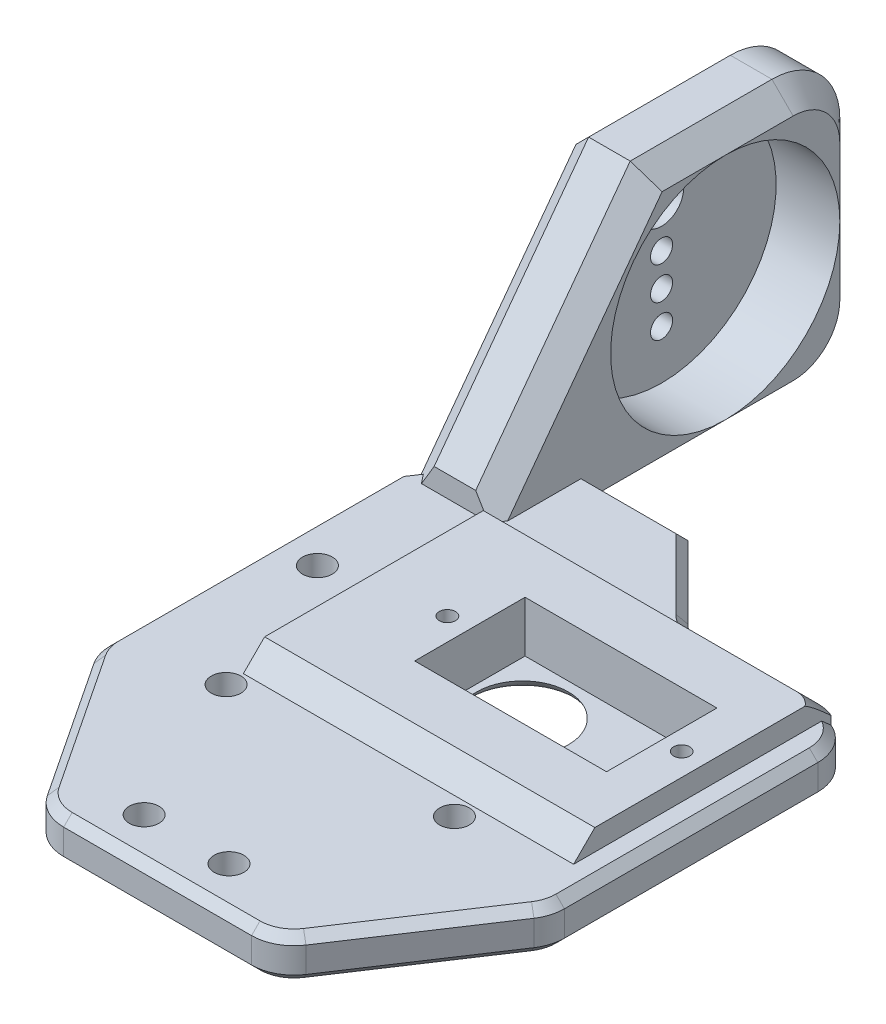
SolidWorks part; units mm, degrees
material "PETG"
ref_plane "Front Plane" through (0, 0, 0) normal (0, 0, 1) x (1, 0, 0)
ref_plane "Top Plane" through (0, 0, 0) normal (0, 1, 0) x (1, 0, 0)
ref_plane "Right Plane" through (0, 0, 0) normal (1, 0, 0) x (0, 0, -1)
sketch "Sketch1" plane through (0, 0, 0) normal (0, 1, 0) x (1, 0, 0)
  line L0 (0, 0) -> (45, 0) construction
  line L1 (45, 15.3791) -> (45, -15.3791)
  line L2 (45, 15.3791) -> (21, 15.3791)
  line L3 (21, 15.3791) -> (11.0015, 25.3776)
  line L4 (11.0015, 25.3776) -> (-4.9985, 25.3776)
  line L5 (-4.9985, 25.3776) -> (-12.2574, 14.4891)
  line L6 (-12.2574, 14.4891) -> (-12.2574, -20.9073)
  line L7 (-12.2574, -20.9073) -> (0.7918, -40.6224)
  line L10 (28.2918, -40.6224) -> (45, -15.3791)
  line L11 (28.2918, -40.6224) -> (0.7918, -40.6224)
  point P6 (45, 0)
  dimension "D2" = 24
  dimension "D3" = 14.14
  dimension "D4" = 225
  dimension "D5" = 16
  dimension "D6" = 27.5
  dimension "D7" = 30.272
  dimension "D8" = 146.31
  dimension "D9" = 123.5
  dimension "D10" = 123.5
  dimension "D11" = 23.6425
  dimension "D13" = 45
  dimension "D1267.5" = 66
extrude "Boss-Extrude1" add sketch "Sketch1" along normal blind 5
sketch "Sketch2" plane through (0, 5, 0) normal (0, 1, 0) x (1, 0, 0)
  line L0 (45, 0) -> (-23.0301, 0) construction
  line L1 (45, -15.3791) -> (45, 15.3791) construction
  line L3 (-12.2574, 14.4891) -> (-12.2574, -20.9073) construction
  line L9 (11.5, 5.4) -> (22.3, 5.4)
  line L10 (11.5, 5.4) -> (11.5, -5.4)
  line L11 (11.5, -5.4) -> (22.3, -5.4)
  line L12 (22.3, 5.4) -> (22.3, -5.4)
  line L13 (11.5, 5.4) -> (22.3, -5.4) construction
  line L14 (11.5, -5.4) -> (22.3, 5.4) construction
  circle A0 centre (-7.2574, 0) radius 1.75
  point P9 (-12.2574, -3.2091)
  point P23 (16.9, 0)
  dimension "D2" = 3.5
  dimension "D6" = 10.8
  dimension "D1" = 5
  dimension "D7" = 10.8
  dimension "D8" = 22.7
extrude "Cut-Extrude1" cut sketch "Sketch2" against normal through all
fillet "Fillet1" radius 5.4 4 edges at (11.5, 0, 0) (11.5, 2.5, 5.4) (11.5, 2.5, -5.4) (11.5, 5, 0)
fillet "Fillet2" radius 5.4 8 edges at (22.3, 0, 0) (22.3, 2.5, -5.4) (22.3, 2.5, 5.4) (19.6, 0, -5.4) (22.3, 5, 0) (19.6, 5, -5.4) (19.6, 5, 5.4) (19.6, 0, 5.4)
sketch "Sketch3" plane through (0, 5, 0) normal (0, 1, 0) x (1, 0, 0)
  line L0 (11.5, 0) -> (22.3, 0) construction
  line L1 (45, 15.3791) -> (21, 15.3791) construction
  line L2 (5.4, -6.5) -> (28.4, -6.5)
  line L3 (5.4, -6.5) -> (5.4, 6.5)
  line L4 (5.4, 6.5) -> (28.4, 6.5)
  line L5 (28.4, -6.5) -> (28.4, 6.5)
  line L6 (5.4, -6.5) -> (28.4, 6.5) construction
  line L7 (5.4, 6.5) -> (28.4, -6.5) construction
  line L8 (-0.6, -15.3791) -> (34.4, -15.3791)
  line L9 (-0.6, -15.3791) -> (-0.6, 15.3791)
  line L10 (-0.6, 15.3791) -> (34.4, 15.3791)
  line L11 (34.4, -15.3791) -> (34.4, 15.3791)
  line L12 (-0.6, -15.3791) -> (34.4, 15.3791) construction
  line L13 (-0.6, 15.3791) -> (34.4, -15.3791) construction
  arc A0 (16.9, 5.4) -> (16.9, -5.4) centre (16.9, 0) ccw construction
  arc A1 (16.9, -5.4) -> (16.9, 5.4) centre (16.9, 0) ccw construction
  point P8 (16.9, 0)
  point P13 (16.9, 0)
  dimension "D1" = 6
  dimension "D2" = 13
  dimension "D3" = 23
extrude "Boss-Extrude2" add sketch "Sketch3" along normal blind 2.5
sketch "Sketch4" plane through (0, 5, 0) normal (0, 1, 0) x (1, 0, 0)
  line L4 (5.4, 6.5) -> (5.4, -6.5)
  line L6 (5.4, 6.5) -> (5.4, -6.5)
  line L12 (5.4, -6.5) -> (28.4, -6.5)
  line L13 (5.4, -6.5) -> (28.4, -6.5)
  line L14 (28.4, -6.5) -> (28.4, 6.5)
  line L15 (28.4, -6.5) -> (28.4, 6.5)
  line L16 (28.4, 6.5) -> (5.4, 6.5)
  line L17 (28.4, 6.5) -> (5.4, 6.5)
  dimension "D1" = 0
extrude "Cut-Extrude2" cut sketch "Sketch4" against normal blind 3.5
fillet "Fillet4" radius 4 2 edges at (34.4, 6.25, 15.3791) (34.4, 6.25, -15.3791)
sketch "Sketch6" plane through (0, 0, -25.3776) normal (0, 0, -1) x (-1, 0, 0)
  line L0 (4.9985, 5) -> (4.9985, 0) construction
  line L1 (0.6, 0) -> (10.9985, 0)
  line L2 (0.6, 0) -> (0.6, 32)
  line L3 (0.6, 32) -> (10.9985, 32)
  line L4 (10.9985, 0) -> (10.9985, 32)
  line L5 (-11.0015, 0) -> (4.9985, 0) construction
  line L6 (0.6, 7.5) -> (0.6, 5) construction
  dimension "D2" = 6
  dimension "D3" = 32
extrude "Boss-Extrude3" add sketch "Sketch6" along normal blind 32
fillet "Fillet5" radius 8 2 edges at (-5.7992, 0, -57.3776) (-5.7992, 32, -57.3776)
sketch "Sketch8" plane through (-10.9985, 0, 0) normal (-1, 0, 0) x (0, 0, 1)
  line L1 (-25.3776, 32) -> (-25.3776, 0)
  line L4 (-25.3776, 0) -> (-14.4891, 0)
  line L5 (-14.4891, 0) -> (-14.4891, 7.5)
  line L6 (-15.3791, 7.5) -> (15.3791, 7.5) construction
  line L7 (-25.3776, 32) -> (-14.4891, 7.5)
extrude "Boss-Extrude4" add sketch "Sketch8" against normal up to surface (10.3985 mm away) up to face at (-0.6, 14.4286, -41.8509)
sketch "Sketch10" plane through (-10.9985, 0, 0) normal (-1, 0, 0) x (0, 0, 1)
  line L0 (-14.4891, 7.5) -> (-32.6851, 32)
  line L1 (-49.3776, 32) -> (-25.3776, 32) construction
  line L2 (-32.6851, 32) -> (-25.3776, 32)
  line L3 (-25.3776, 32) -> (-14.4891, 7.5)
  line L4 (-49.3776, 32) -> (-25.3776, 32) construction
  line L5 (-14.4891, 7.5) -> (-25.3776, 32) construction
  dimension "D2" = 30.5179
extrude "Cut-Extrude6" cut sketch "Sketch10" against normal through all
sketch "Sketch11" plane through (0, 1.5, 0) normal (0, 1, 0) x (1, 0, 0)
  line L0 (5.4, -6.5) -> (28.4, -6.5) construction
  line L1 (5.4, 6.5) -> (10.7, 6.5)
  line L2 (5.4, 6.5) -> (5.4, -6.5)
  line L3 (5.4, -6.5) -> (10.7, -6.5)
  line L4 (10.7, 6.5) -> (10.7, -6.5)
  line L5 (5.4, 0) -> (10.7, 0) construction
  circle A0 centre (8.05, 0) radius 0.95
  dimension "D2" = 1.9
  dimension "D1" = 5.3
extrude "Boss-Extrude5" add sketch "Sketch11" along normal up to surface (6 mm away) up to face at (18.4938, 7.5, -2.0699)
sketch "Sketch12" plane through (0, 7.5, 0) normal (0, 1, 0) x (1, 0, 0)
  line L0 (30.4, 15.3791) -> (38.3, 15.3791)
  line L1 (38.3, 15.3791) -> (38.3, -15.3791)
  line L2 (30.4, -15.3791) -> (38.3, -15.3791)
  line L3 (34.4, -11.3791) -> (34.4, 11.3791) construction
  line L4 (34.4, -11.3791) -> (34.4, 11.3791)
  arc A0 (30.4, -15.3791) -> (34.4, -11.3791) centre (30.4, -11.3791) ccw construction
  arc A1 (34.4, 11.3791) -> (30.4, 15.3791) centre (30.4, 11.3791) ccw construction
  arc A2 (30.4, -15.3791) -> (34.4, -11.3791) centre (30.4, -11.3791) ccw
  arc A3 (34.4, 11.3791) -> (30.4, 15.3791) centre (30.4, 11.3791) ccw
  dimension "D1" = 7.9
extrude "Boss-Extrude6" add sketch "Sketch12" against normal up to surface (7.5 mm away)
sketch "Sketch13" plane through (0, 7.5, 0) normal (0, 1, 0) x (1, 0, 0)
  line L0 (8.05, 0) -> (35.65, 0) construction
  circle A0 centre (35.65, 0) radius 0.95
  dimension "D2" = 1.9
  dimension "D1" = 27.6
extrude "Cut-Extrude7" cut sketch "Sketch13" against normal up to surface (6 mm away) up to face at (8.05, 1.5, 0.95)
sketch "Sketch14" plane through (0, 7.5, 0) normal (0, 1, 0) x (1, 0, 0)
  line L1 (28.4, 6.5) -> (33.3, 6.5)
  line L2 (28.4, 6.5) -> (28.4, -6.5)
  line L3 (28.4, -6.5) -> (33.3, -6.5)
  line L4 (33.3, 6.5) -> (33.3, -6.5)
  dimension "D1" = 4.9
extrude "Cut-Extrude8" cut sketch "Sketch14" against normal up to surface (6 mm away) up to face at (19.55, 1.5, 0)
fillet "Fillet11" radius 2.5 2 edges at (11.5, 0, 0) (22.3, 0, 0)
sketch "Sketch16" plane through (0, 0, 0) normal (0, -1, 0) x (1, 0, 0)
  line L0 (16.75, 0) -> (26.4024, 17.5166) construction
  line L1 (26.4024, 17.5166) -> (-0.4976, 17.5166) construction
  line L2 (-2.5177, 35.6224) -> (31.6012, 35.6224) construction
  line L3 (-12.2574, 20.9073) -> (0.7918, 40.6224) construction
  line L4 (28.2918, 40.6224) -> (45, 15.3791) construction
  line L6 (12.9524, 17.5166) -> (12.9524, 35.6224) construction
  line L7 (0.7918, 40.6224) -> (28.2918, 40.6224) construction
  circle A0 centre (26.4024, 17.5166) radius 1.75
  circle A1 centre (-0.4976, 17.5166) radius 1.75
  circle A2 centre (7.9524, 35.6224) radius 1.75
  circle A3 centre (17.9524, 35.6224) radius 1.75
  dimension "D1" = 3.5
  dimension "D5" = 3.5
  dimension "D2" = 26.9
  dimension "D3" = 5
  dimension "D4" = 10
  dimension "D6" = 5
extrude "Cut-Extrude10" cut sketch "Sketch16" against normal up to surface (5 mm away) up to face at (-7.2574, 5, 1.75)
sketch "Sketch17" plane through (38.3, 0, 0) normal (1, 0, 0) x (0, 0, -1)
  line L1 (15.3791, 7.5) -> (-40.6224, 7.5)
  line L2 (15.3791, 7.5) -> (15.3791, 0)
  line L3 (15.3791, 0) -> (-40.6224, 0)
  line L4 (-40.6224, 7.5) -> (-40.6224, 0)
  line L6 (15.3791, 5) -> (15.3791, 7.5) construction
  line L7 (15.3791, 7.5) -> (15.3791, 5) construction
  line L8 (-15.3791, 7.5) -> (15.3791, 7.5) construction
  line L9 (-40.6224, 5) -> (-40.6224, 0) construction
extrude "Cut-Extrude11" cut sketch "Sketch17" along normal up to surface (3.7 mm away) from offset 3 up to face at (45, 2.5, 0)
fillet "Fillet13" radius 5 2 edges at (41.3, 2.5, 20.9692) (41.3, 2.5, -15.3791)
sketch "Sketch19" plane through (-0.6, 0, 0) normal (1, 0, 0) x (0, 0, -1)
  line L0 (57.3776, 24) -> (57.3776, 8) construction
  line L1 (49.3776, 0) -> (25.3776, 0) construction
  circle A0 centre (41.3776, 16) radius 13.5
  dimension "D1" = 27
  dimension "D2" = 16
  dimension "D3" = 16
extrude "Cut-Extrude13" cut sketch "Sketch19" against normal blind 7.5 contours A0
sketch "Sketch20" plane through (-8.1, 0, 0) normal (1, 0, 0) x (0, 0, -1)
  line L0 (41.3776, 29.5) -> (41.3776, 2.5) construction
  circle A0 centre (41.3776, 16) radius 13.5 construction
  circle A1 centre (41.3776, 16) radius 13.5 construction
  circle A2 centre (41.3776, 21.1) radius 2.6
  circle A3 centre (41.3776, 16) radius 1.3
  circle A4 centre (41.3776, 12.14) radius 1.3
  circle A5 centre (41.3776, 8.28) radius 1.3
  dimension "D2" = 5.2
  dimension "D4" = 2.6
  dimension "D1" = 8.4
  dimension "D3" = 5.1
  dimension "D5" = 3.86
  dimension "D6" = 3.86
extrude "Cut-Extrude14" cut sketch "Sketch20" against normal up to surface (2.8985 mm away) up to face at (-10.9985, 12.6111, -34.5825)
chamfer "Chamfer1" distance 2.5 angle 45 3 edges at (37.3215, 7.5, -15.2736) (17.85, 7.5, -15.3791) (18.85, 7.5, 15.3791)
fillet "Fillet15" radius 5 4 edges at (-12.2574, 2.5, 20.9073) (21, 2.5, -15.3791) (0.7918, 2.5, 40.6224) (28.2918, 2.5, 40.6224)
chamfer "Chamfer2" distance 1 angle 45 28 edges at (-12.2574, 0, 2.4566) (-12.2574, 5, 2.4566) (-12.0453, 5, 20.8434) (-12.0453, 0, 20.8434) (-6.059, 5, 30.2721) (-6.059, 0, 30.2721) (1.1118, 5, 40.0269) (1.1118, 0, 40.0269) (14.5418, 5, 40.6224) (14.5418, 0, 40.6224) (27.9718, 5, 40.0269) (27.9718, 0, 40.0269) (35.122, 5, 30.3031) (35.122, 0, 30.3031) (41.0879, 0, 20.9053) (41.0879, 5, 20.9053) (41.3, 5, 4.5426) (41.3, 0, 4.5426) (39.8355, 0, -13.9146) (29.6855, 0, -15.3791) (21.1577, 5, -15.7597) (21.1577, 0, -15.7597) (15.2685, 5, -21.1105) (15.2685, 0, -21.1105) (5.2008, 5, -25.3776) (5.2008, 0, -25.3776) (40.4833, 5, -13.1177) (-11.628, 5, -15.4333)
chamfer "Chamfer3" distance 3 angle 45 6 edges at (-10.9985, 0, -32.8775) (-10.9985, 2.3431, -55.0344) (-10.9985, 16, -57.3776) (-10.9985, 29.6569, -55.0344) (-10.9985, 19.75, -23.5871) (-10.9985, 32, -41.0313)
chamfer "Chamfer4" distance 2.5 angle 45 6 edges at (-0.6, 0, -36.8776) (-0.6, 2.3431, -55.0344) (-0.6, 16, -57.3776) (-0.6, 29.6569, -55.0344) (-0.6, 32, -41.0313) (-0.6, 19.75, -23.5871)
